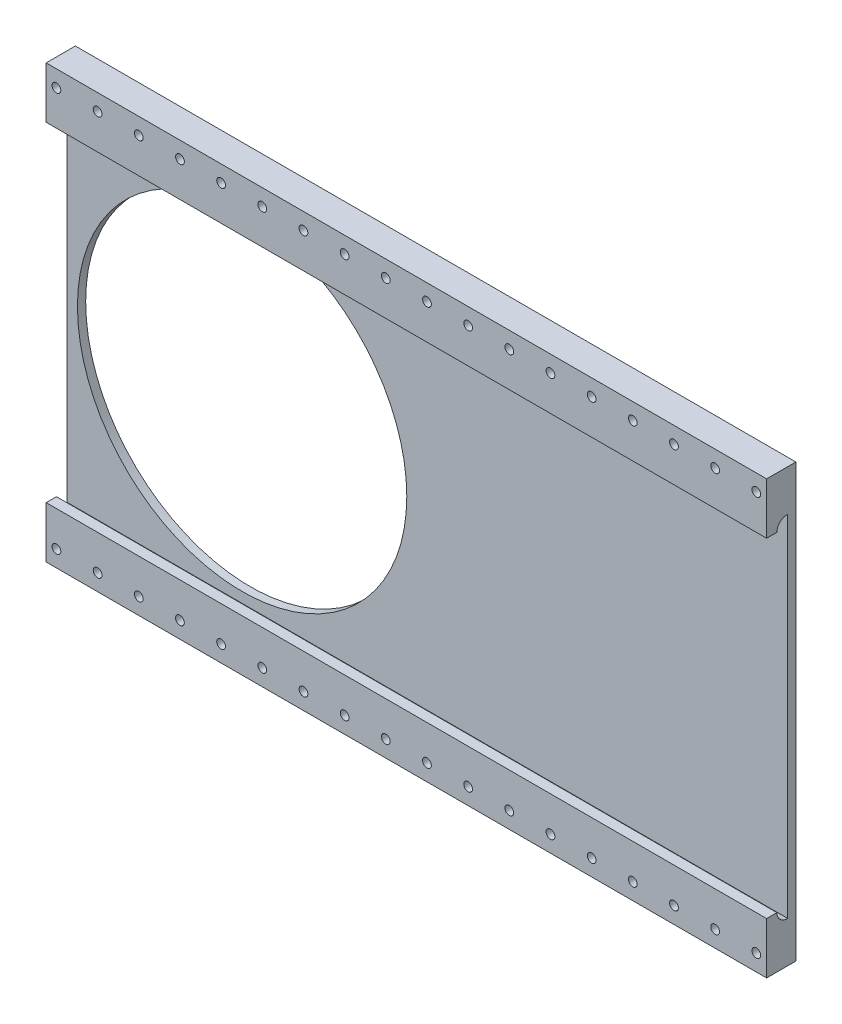
SolidWorks part; units mm, degrees
material "PET"
ref_plane "Front Plane" through (0, 0, 0) normal (0, 0, 1) x (1, 0, 0)
ref_plane "Top Plane" through (0, 0, 0) normal (0, 1, 0) x (1, 0, 0)
ref_plane "Right Plane" through (0, 0, 0) normal (1, 0, 0) x (0, 0, -1)
sketch "Sketch1" plane through (0, 0, 0) normal (0, 0, 1) x (1, 0, 0)
  line L0 (-53.975, 57.15) -> (168.275, 57.15)
  line L1 (168.275, 57.15) -> (168.275, -57.15)
  line L2 (168.275, -57.15) -> (-53.975, -57.15)
  line L3 (-53.975, -57.15) -> (-53.975, 57.15)
  line L4 (-50.8, 0) -> (-53.975, 0) construction
  line L5 (50.8, 0) -> (168.275, 0) construction
  circle A0 centre (0, 0) radius 50.8
  dimension "D1" = 101.6
  dimension "D2" = 3.175
  dimension "D3" = 114.3
  dimension "D4" = 117.475
extrude "Boss-Extrude1" add sketch "Sketch1" along normal blind 2.54
sketch "Sketch3" plane through (168.275, 0, 0) normal (1, 0, 0) x (0, 0, -1)
  line L0 (-2.54, 57.15) -> (-9.017, 57.15)
  line L1 (-9.017, 57.15) -> (-9.017, 50.8)
  line L2 (-9.017, 50.8) -> (-5.842, 50.8)
  line L3 (-5.842, 50.8) -> (-5.842, 53.975)
  line L4 (-5.842, 53.975) -> (-2.54, 53.975)
  line L5 (-2.54, -57.15) -> (-2.54, 57.15) construction
  line L6 (-2.54, 57.15) -> (-2.54, 53.975)
  dimension "D1" = 6.477
  dimension "D2" = 6.35
  dimension "D3" = 3.175
  dimension "D4" = 3.175
extrude "Boss-Extrude2" add sketch "Sketch3" against normal up to surface (222.25 mm away) up to face at (-53.975, 0, 1.27)
ref_plane "Plane1" through (0, 0, 0) normal (0, -1, 0) x (-1, 0, 0)
mirror "Mirror1" about plane through (0, 0, 0) normal (0, -1, 0) of "Boss-Extrude2"
sketch "Sketch4" plane through (0, 0, 0) normal (0, 0, 1) x (1, 0, 0)
  line L1 (-53.975, -57.15) -> (168.275, -57.15)
  line L2 (-53.975, 57.15) -> (168.275, 57.15)
  line L3 (-53.975, 57.15) -> (-53.975, 66.675)
  line L4 (-53.975, 66.675) -> (168.275, 66.675)
  line L5 (168.275, 57.15) -> (168.275, 66.675)
  line L6 (-53.975, -57.15) -> (-53.975, -66.675)
  line L7 (-53.975, -66.675) -> (168.275, -66.675)
  line L8 (168.275, -57.15) -> (168.275, -66.675)
  point P11 (165.1, -57.15)
  dimension "D1" = 9.525
  dimension "D2" = 9.525
extrude "Boss-Extrude3" add sketch "Sketch4" along normal up to surface (9.017 mm away) up to face at (57.15, 53.975, 9.017)
hole_wizard "#6-32 Tapped Hole1" positions "Sketch6" profile "Sketch7" tap size "#6-32" standard "ANSI Inch" end condition through all
sketch "Sketch6" plane through (0, 0, 9.017) normal (0, 0, 1) x (1, 0, 0)
  line L1 (0, 0) -> (0, 66.675) construction
  line L2 (-53.975, 66.675) -> (168.275, 66.675) construction
  line L4 (0, 0) -> (0, -66.675) construction
  line L5 (-53.975, -66.675) -> (168.275, -66.675) construction
  line L6 (-12.7, 66.675) -> (-12.7, -66.675) construction
  line L8 (-25.4, 66.675) -> (-25.4, -66.675) construction
  line L10 (-38.1, 66.675) -> (-38.1, -66.675) construction
  line L12 (-50.8, 66.675) -> (-50.8, -66.675) construction
  point P17 (-50.8, 61.595)
  point P20 (-50.8, -61.595)
  point P36 (-50.8, -59.0712)
  point P37 (-50.8, 60.7829)
  dimension "D1" = 12.7
  dimension "D2" = 12.7
  dimension "D3" = 12.7
  dimension "D4" = 12.7
  dimension "D5" = 5.08
  dimension "D6" = 5.08
  dimension "D7" = 123.19
sketch "Sketch7" plane through (-50.8, -61.595, 9.017) normal (1, 0, 0) x (0, -1, 0)
  line L0 (0, 0) -> (0, 9.017)
  line L1 (0, 9.017) -> (1.3525, 9.017)
  line L2 (1.3525, 9.017) -> (1.3525, 0)
  line L5 (1.3525, 0) -> (0, 0)
  line L11 (0, -6.35) -> (0, 107.95) construction
  dimension "Thru Tap Drill Dia." = 2.7051
  dimension "Thru Tap Drill Depth" = 9.017
cosmetic thread "Hole Thread1" parameters "D2"=3.5052
cosmetic thread "Hole Thread2" parameters "D2"=3.5052
pattern_linear "LPattern1" count 18 spacing 12.7 along (1, 0, 0) of "#6-32 Tapped Hole1"
fillet "Fillet1" radius 3.175 2 edges at (57.15, 53.975, 5.842) (57.15, -53.975, 5.842)
